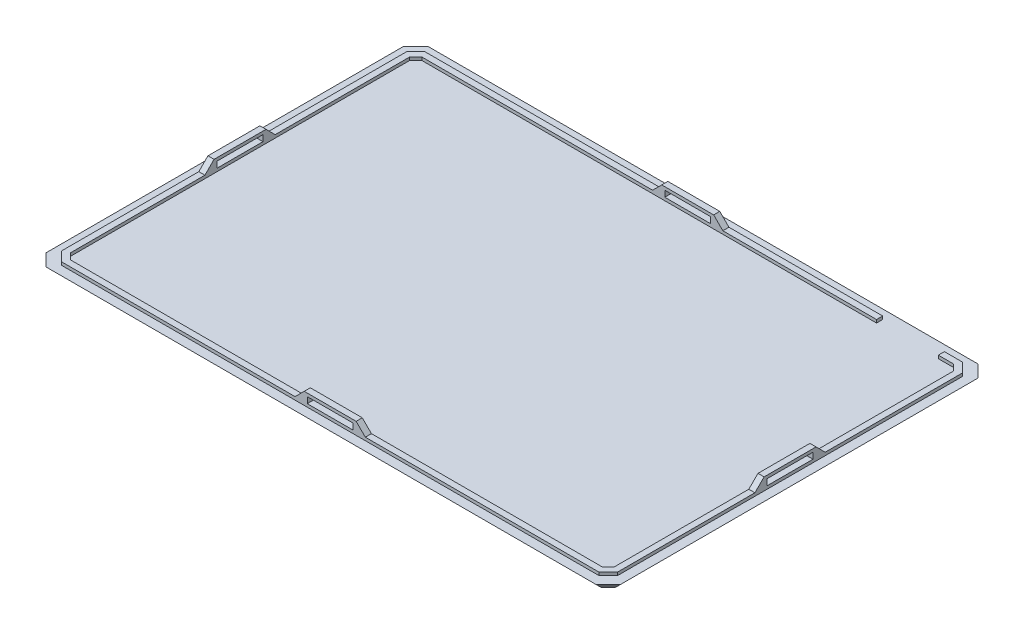
SolidWorks part; units mm, degrees
material "尼龙 101"
ref_plane "前视基准面" through (0, 0, 0) normal (0, 0, 1) x (1, 0, 0)
ref_plane "上视基准面" through (0, 0, 0) normal (0, 1, 0) x (1, 0, 0)
ref_plane "右视基准面" through (0, 0, 0) normal (1, 0, 0) x (0, 0, -1)
sketch "草图1" plane through (0, 0, 0) normal (0, 1, 0) x (1, 0, 0)
  line L1 (94, -62.5) -> (-94, -62.5)
  line L2 (94, -62.5) -> (94, 62.5)
  line L3 (94, 62.5) -> (-94, 62.5)
  line L4 (-94, -62.5) -> (-94, 62.5)
  line L5 (94, -62.5) -> (-94, 62.5) construction
  line L6 (94, 62.5) -> (-94, -62.5) construction
  point P0 (0, 0)
  dimension "D1" = 188
  dimension "D2" = 125
extrude "凸台-拉伸1" add sketch "草图1" against normal blind 3
sketch "草图2" plane through (0, 0, 0) normal (0, 1, 0) x (1, 0, 0)
  line L0 (-94, 62.5) -> (-94, -62.5) construction
  line L1 (91, -59.5) -> (-91, -59.5)
  line L2 (91, -59.5) -> (91, 59.5)
  line L3 (91, 59.5) -> (-91, 59.5)
  line L4 (-91, -59.5) -> (-91, 59.5)
  line L5 (91, -59.5) -> (-91, 59.5) construction
  line L6 (91, 59.5) -> (-91, -59.5) construction
  line L7 (-89, -57.5) -> (89, -57.5)
  line L8 (-89, -57.5) -> (-89, 57.5)
  line L9 (-89, 57.5) -> (89, 57.5)
  line L10 (89, -57.5) -> (89, 57.5)
  line L11 (94, 62.5) -> (-94, 62.5) construction
  point P0 (0, 0)
  dimension "D1" = 2
  dimension "D2" = 2
  dimension "D3" = 115
  dimension "D4" = 178
  dimension "D5" = 3
  dimension "D6" = 3
extrude "凸台-拉伸2" add sketch "草图2" along normal blind 1
sketch "草图4" plane through (0, 0, -59.5) normal (0, 0, -1) x (-1, 0, 0)
  line L0 (-91, 1) -> (91, 1) construction
  line L1 (-82, 1) -> (-61.8, 1)
  line L2 (-82, 1) -> (-82, 0)
  line L3 (-82, 0) -> (-61.8, 0)
  line L4 (-61.8, 1) -> (-61.8, 0)
  line L5 (-91, 0) -> (91, 0) construction
  line L6 (-91, 1) -> (-91, 0) construction
  dimension "D1" = 20.2
  dimension "D2" = 9
extrude "切除-拉伸1" cut sketch "草图4" against normal up to next
sketch "草图5" plane through (0, 1, 0) normal (0, 1, 0) x (1, 0, 0)
  line L0 (-91, -59.5) -> (91, -59.5) construction
  line L1 (-7.5, -59.5) -> (7.5, -59.5)
  line L2 (-7.5, -59.5) -> (-7.5, -57.5)
  line L3 (-7.5, -57.5) -> (7.5, -57.5)
  line L4 (7.5, -59.5) -> (7.5, -57.5)
  line L5 (-89, -57.5) -> (89, -57.5) construction
  line L6 (89, -57.5) -> (89, 57.5) construction
  line L7 (89, -7.5) -> (91, -7.5)
  line L8 (89, -7.5) -> (89, 7.5)
  line L9 (89, 7.5) -> (91, 7.5)
  line L10 (91, -7.5) -> (91, 7.5)
  line L11 (91, -59.5) -> (91, 59.5) construction
  line L12 (-91, 59.5) -> (-91, -59.5) construction
  line L13 (-94, 0) -> (93.881, 0) construction
  line L14 (-94, 62.5) -> (-94, -62.5) construction
  line L15 (0, 62.5) -> (0, -62.3787) construction
  line L16 (94, 62.5) -> (-94, 62.5) construction
  line L17 (-7.5, 57.5) -> (7.5, 57.5)
  line L18 (7.5, 59.5) -> (7.5, 57.5)
  line L19 (-7.5, 59.5) -> (7.5, 59.5)
  line L20 (-7.5, 59.5) -> (-7.5, 57.5)
  line L21 (-89, 7.5) -> (-91, 7.5)
  line L22 (-91, -7.5) -> (-91, 7.5)
  line L23 (-89, -7.5) -> (-91, -7.5)
  line L24 (-89, -7.5) -> (-89, 7.5)
  point P16 (90, 7.5)
  dimension "D1" = 15
  dimension "D2" = 15
  dimension "D3" = 83.5
  dimension "D4" = 52
extrude "凸台-拉伸3" add sketch "草图5" along normal blind 3
chamfer "倒角1" distance 4 angle 45 8 edges at (-90, 1, -7.5) (-90, 1, 7.5) (-7.5, 1, 58.5) (7.5, 1, 58.5) (90, 1, 7.5) (90, 1, -7.5) (-7.5, 1, -58.5) (7.5, 1, -58.5)
sketch "草图6" plane through (0, 0, -59.5) normal (0, 0, -1) x (-1, 0, 0)
  line L0 (-11.5, 1) -> (11.5, 1) construction
  line L1 (0, 4) -> (0, -3) construction
  line L2 (-7.5, 1) -> (7.5, 1)
  line L3 (-7.5, 1) -> (-7.5, 3)
  line L4 (-7.5, 3) -> (7.5, 3)
  line L5 (7.5, 1) -> (7.5, 3)
  line L6 (-8.5, 4) -> (8.5, 4) construction
  line L7 (-94, -3) -> (94, -3) construction
  point P8 (7.5, 2)
  dimension "D1" = 2
  dimension "D2" = 15
  dimension "D3" = 7.5
extrude "切除-拉伸2" cut sketch "草图6" against normal up to surface (119 mm away) up to face at (0, 1.5, 59.5)
sketch "草图7" plane through (-91, 0, 0) normal (-1, 0, 0) x (0, 0, 1)
  line L0 (0, 4) -> (0, -3) construction
  line L1 (-8.5, 4) -> (8.5, 4) construction
  line L2 (-62.5, -3) -> (62.5, -3) construction
  line L3 (-11.5, 1) -> (11.5, 1) construction
  line L5 (-7.5, 1) -> (7.5, 1)
  line L6 (-7.5, 1) -> (-7.5, 3)
  line L7 (-7.5, 3) -> (7.5, 3)
  line L8 (7.5, 1) -> (7.5, 3)
  point P14 (-7.5, 2)
  dimension "D1" = 7.5
  dimension "D2" = 15
  dimension "D3" = 2
extrude "切除-拉伸3" cut sketch "草图7" against normal up to surface (182 mm away) up to face at (91, 1.5, 0)
sketch "草图8" plane through (0, -3, 0) normal (0, -1, 0) x (1, 0, 0)
  line L0 (-94, 62.5) -> (94, 62.5) construction
  line L1 (-94, -62.5) -> (-94, 62.5) construction
  line L2 (-94, 0) -> (94, 0) construction
  line L3 (94, 62.5) -> (94, -62.5) construction
  line L4 (0, 62.5) -> (0, -62.5) construction
  line L5 (94, -62.5) -> (-94, -62.5) construction
  circle A0 centre (-64, 37.5) radius 12.5
  circle A1 centre (-64, -37.5) radius 12.5
  circle A2 centre (64, 37.5) radius 12.5
  circle A3 centre (64, -37.5) radius 12.5
  dimension "D1" = 25
  dimension "D2" = 25
  dimension "D3" = 30
extrude "凸台-拉伸4" add sketch "草图8" along normal blind 2
sketch "草图9" plane through (0, -3, 0) normal (0, -1, 0) x (1, 0, 0)
  line L0 (-94, 0) -> (94, 0) construction
  line L1 (-94, -62.5) -> (-94, 62.5) construction
  line L2 (94, 62.5) -> (94, -62.5) construction
  line L3 (0, 62.5) -> (0, -62.5) construction
  line L4 (-94, 62.5) -> (94, 62.5) construction
  line L5 (94, -62.5) -> (-94, -62.5) construction
  circle A0 centre (-64, 37.5) radius 10
  circle A1 centre (-64, -37.5) radius 10
  circle A2 centre (64, 37.5) radius 10
  circle A3 centre (64, -37.5) radius 10
  dimension "D1" = 20
extrude "切除-拉伸4" cut sketch "草图9" along normal blind 2
chamfer "倒角2" distance 4 angle 45 4 edges at (94, -1.5, -62.5) (-94, -1.5, -62.5) (-94, -1.5, 62.5) (94, -1.5, 62.5)
chamfer "倒角3" distance 3 angle 45 8 edges at (92, -3, -60.5) (0, -3, -62.5) (-92, -3, -60.5) (-94, -3, 0) (-92, -3, 60.5) (0, -3, 62.5) (92, -3, 60.5) (94, -3, 0)
chamfer "倒角4" distance 2 angle 45 4 edges at (-89, 0.5, 57.5) (89, 0.5, 57.5) (89, 0.5, -57.5) (-89, 0.5, -57.5)
chamfer "倒角5" distance 3 angle 45 4 edges at (-91, 0.5, -59.5) (-91, 0.5, 59.5) (91, 0.5, 59.5) (91, 0.5, -59.5)
